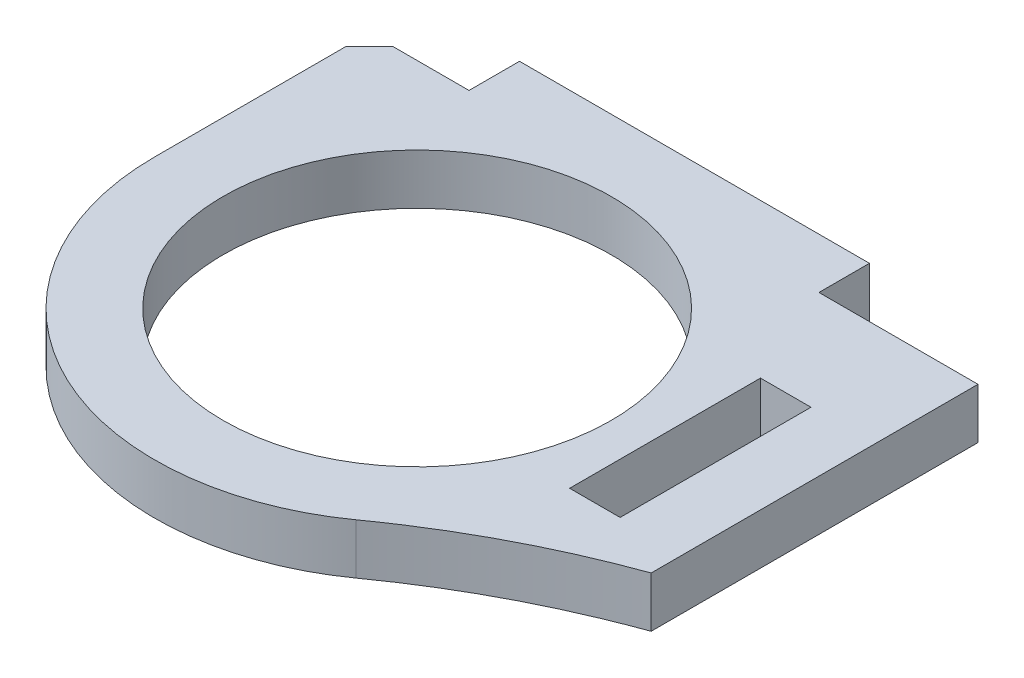
SolidWorks part; units mm, degrees
ref_plane "Front Plane" through (0, 0, 0) normal (0, 0, 1) x (1, 0, 0)
ref_plane "Top Plane" through (0, 0, 0) normal (0, 1, 0) x (1, 0, 0)
ref_plane "Right Plane" through (0, 0, 0) normal (1, 0, 0) x (0, 0, -1)
sketch "Sketch1" plane through (0, 0, 0) normal (0, 1, 0) x (1, 0, 0)
  line L0 (-16.5, 0) -> (-12.2, 0)
  line L1 (-12.2, 0) -> (-12.2, 18)
  line L2 (-16.5, 0) -> (-16.5, 18)
  line L3 (-16.5, 18) -> (-12.2, 18)
  line L4 (12.2, 0) -> (16.5, 0)
  line L5 (16.5, 0) -> (16.5, 18.6135)
  line L6 (12.2, 0) -> (12.2, 18.6135)
  line L7 (12.2, 18.6135) -> (16.5, 18.6135)
  line L8 (-20.5383, 16.5) -> (20.5383, 16.5)
  circle A0 centre (0, 0) radius 12.2
  circle A1 centre (0, 0) radius 16.5
  point P15 (0, 16.5)
  dimension "D1" = 24.4
  dimension "D2" = 33
  dimension "D3" = 18
extrude "Boss-Extrude1" add sketch "Sketch1" along normal blind 3.175 contours A1 L1 L8 L2 | A1 L5 L8 L6 | L4 A1 L6 | L1 A1 L0 | L0 A1 L4 A0
sketch "Sketch2" plane through (0, 3.175, 0) normal (0, 1, 0) x (1, 0, 0)
  line L0 (16.5, 0) -> (16.5, 18.6135) construction
  line L1 (16.5, 11.5) -> (19.675, 11.5)
  line L2 (16.5, 11.5) -> (16.5, -2.5)
  line L3 (16.5, -2.5) -> (19.675, -2.5)
  line L4 (19.675, 11.5) -> (19.675, -2.5)
  line L6 (15.2, -4.5) -> (15.8745, -4.5)
  line L7 (15.2, 15.5) -> (23.375, 15.5)
  line L8 (15.2, 15.5) -> (15.2, -4.5)
  line L9 (15.2, -4.5) -> (23.375, -4.5)
  line L10 (23.375, 15.5) -> (23.375, -4.5)
  line L11 (12.2, 0) -> (12.2, 18.6135) construction
  arc A0 (-16.5, 0) -> (16.5, 0) centre (0, 0) ccw construction
  circle A1 centre (0, 0) radius 15.5
  arc M13 (-16.5, 0) -> (16.5, 0) centre (0, 0) ccw
  line M14 (16.5, 0) -> (16.5, 18.6135)
  dimension "D1" = 3.175
  dimension "D2" = 14
  dimension "D3" = 3
  dimension "D4" = 8.175
  dimension "D5" = 20
  dimension "D6" = 4
extrude "Boss-Extrude2" add sketch "Sketch2" against normal up to surface (3.175 mm away) contours L8 L6 M13 | L10 L7 L1 L4 L3 L8 L9 M14
sketch "Sketch3" plane through (0, 0, 0) normal (0, -1, 0) x (-1, 0, 0)
  line L0 (0, -16.5) -> (-23.375, -16.5)
  line L1 (-23.375, -16.5) -> (-23.375, -4.5)
  line L2 (-15.8745, -4.5) -> (-23.375, -4.5)
  arc A0 (-15.8745, -4.5) -> (16.5, 0) centre (0, 0) ccw construction
  circle A1 centre (0, 0) radius 15.5
  line M7 (-23.375, -4.5) -> (-15.8745, -4.5)
  arc M8 (-15.8745, -4.5) -> (16.5, 0) centre (0, 0) ccw
extrude "Boss-Extrude3" add sketch "Sketch3" against normal up to surface (3.175 mm away) contours L1 L0 M8 M7 up to face at (5.5151, 3.175, -6.2667)
sketch "Sketch5" plane through (0, 3.175, 0) normal (0, 1, 0) x (1, 0, 0)
  line L0 (19.675, -2.5) -> (19.675, -6.5)
  line L1 (19.675, -6.5) -> (23.375, -6.5)
  line L2 (23.375, 15.5) -> (23.375, -16.5) construction
  line L3 (23.375, -6.5) -> (23.375, -16.5)
  line L4 (23.375, -16.5) -> (12.1655, -16.5)
  line L5 (0, -16.5) -> (23.375, -16.5) construction
  line L6 (19.675, -6.5) -> (17.4914, -6.5)
  line L7 (17.4914, -6.5) -> (13.4811, -6.5)
  line L8 (12.1655, -16.5) -> (0, -16.5)
  circle A0 centre (0, 0) radius 16.5
  line M3 (0, -16.5) -> (23.375, -16.5)
  line M4 (23.375, -16.5) -> (23.375, 15.5)
  dimension "D2" = 4
extrude "Cut-Extrude2" cut sketch "Sketch5" against normal blind 10 contours A0 L1 L6 L7 M3 M4
fillet "Fillet1" radius 50 1 edges at (15.1658, 1.5875, 6.5)
sketch "Sketch6" plane through (0, 0, -15.5) normal (0, 0, -1) x (-1, 0, 0)
  line L1 (-23.375, 3.175) -> (-16.5, 3.175)
  line L2 (-23.375, 3.175) -> (-23.375, 0)
  line L3 (-23.375, 0) -> (-16.5, 0)
  line L4 (-16.5, 3.175) -> (-16.5, 0)
extrude "Boss-Extrude5" add sketch "Sketch6" along normal up to surface (3.1135 mm away) up to face at (14.35, 1.5875, -18.6135)
sketch "Sketch7" plane through (0, 0, -18.6135) normal (0, 0, -1) x (-1, 0, 0)
  line L1 (-23.375, 3.175) -> (-12.2, 3.175)
  line L2 (-23.375, 3.175) -> (-23.375, 0)
  line L3 (-23.375, 0) -> (-12.2, 0)
  line L4 (-12.2, 3.175) -> (-12.2, 0)
  line L5 (12.2, 3.175) -> (16.5, 3.175)
  line L6 (12.2, 3.175) -> (12.2, 0)
  line L7 (12.2, 0) -> (16.5, 0)
  line L8 (16.5, 3.175) -> (16.5, 0)
extrude "Cut-Extrude3" cut sketch "Sketch7" against normal blind 5.1135
sketch "Sketch8" plane through (0, 3.175, 0) normal (0, 1, 0) x (1, 0, 0)
  line L0 (-12.2, 0) -> (-12.2, 13.5)
  line L1 (-12.2, 13.5) -> (12.2, 13.5)
  line L2 (12.2, 13.5) -> (12.2, 0)
  circle A0 centre (0, 0) radius 12.2
  line M7 (12.2, 13.5) -> (12.2, 0)
  line M9 (-12.2, 0) -> (-12.2, 13.5)
extrude "Boss-Extrude6" add sketch "Sketch8" against normal up to surface (3.175 mm away) contours A0 L1 M7 M9 up to face at (18.0875, 0, -4.5)
sketch "Sketch9" plane through (0, 0, 0) normal (0, -1, 0) x (-1, 0, 0)
  line L1 (-16.5, -2.5) -> (-19.675, -2.5)
  line L2 (-16.5, -2.5) -> (-16.5, 11.5)
  line L3 (-16.5, 11.5) -> (-19.675, 11.5)
  line L4 (-19.675, -2.5) -> (-19.675, 11.5)
extrude "Boss-Extrude7" add sketch "Sketch9" against normal up to surface (3.175 mm away) up to face at (0.6811, 3.175, -4.0651)
sketch "Sketch10" plane through (0, 0, 0) normal (0, -1, 0) x (-1, 0, 0)
  line L0 (-23.375, 13.5) -> (16.5, 13.5) construction
  line L1 (-14.5866, 7) -> (-17.7616, 7)
  line L2 (-14.5866, 7) -> (-14.5866, -5)
  line L3 (-14.5866, -5) -> (-17.7616, -5)
  line L4 (-17.7616, 7) -> (-17.7616, -5)
  line L5 (-23.375, -6.5) -> (-23.375, 13.5) construction
  dimension "D1" = 12
  dimension "D2" = 3.175
  dimension "D3" = 6.5
  dimension "D4" = 5.6134
extrude "Cut-Extrude4" cut sketch "Sketch10" against normal up to surface (3.175 mm away) up to face at (0.6811, 3.175, -4.0651)
sketch "Sketch12" plane through (0, 0, 0) normal (0, -1, 0) x (-1, 0, 0)
  line L0 (-17.7616, 15.1688) -> (-17.7616, -13.1688)
  line L3 (-17.7616, -8.6802) -> (-21.7616, -8.6802)
  line L4 (-17.7616, -8.6802) -> (-17.7616, 14.1816)
  line L5 (-17.7616, 14.1816) -> (-21.7616, 14.1816)
  line L6 (-21.7616, -8.6802) -> (-21.7616, 14.1816)
  line L7 (-21.7616, -7.6776) -> (-25.3865, -7.6776)
  line L8 (-21.7616, -7.6776) -> (-21.7616, 14.1816)
  line L9 (-21.7616, 14.1816) -> (-25.3865, 14.1816)
  line L10 (-25.3865, -7.6776) -> (-25.3865, 14.1816)
  parabola Q0 (-23.375, -6.5) -> (-9.5932, -13.4246) focus (-27.3036, -31.4959) apex (-16.2139, -9.4245) construction
  point P3 (-17.7616, 1)
  dimension "D1" = 4
extrude "Cut-Extrude5" cut sketch "Sketch12" against normal blind 10
sketch "Sketch14" plane through (0, 0, -13.5) normal (0, 0, -1) x (-1, 0, 0)
  line L0 (-9.5932, 3.175) -> (-21.7616, 3.175) construction
  line L1 (-11.7616, 3.175) -> (10.2384, 3.175)
  line L2 (-11.7616, 3.175) -> (-11.7616, 0)
  line L3 (-11.7616, 0) -> (10.2384, 0)
  line L4 (10.2384, 3.175) -> (10.2384, 0)
  line L5 (-21.7616, 0) -> (16.5, 0) construction
  line L8 (-21.7616, 3.175) -> (-21.7616, 0) construction
  dimension "D1" = 22
  dimension "D2" = 10
extrude "Boss-Extrude8" add sketch "Sketch14" along normal blind 3.175
chamfer "Chamfer1" distance 1.5 angle 45 1 edges at (-16.5, 1.5875, -13.5)
